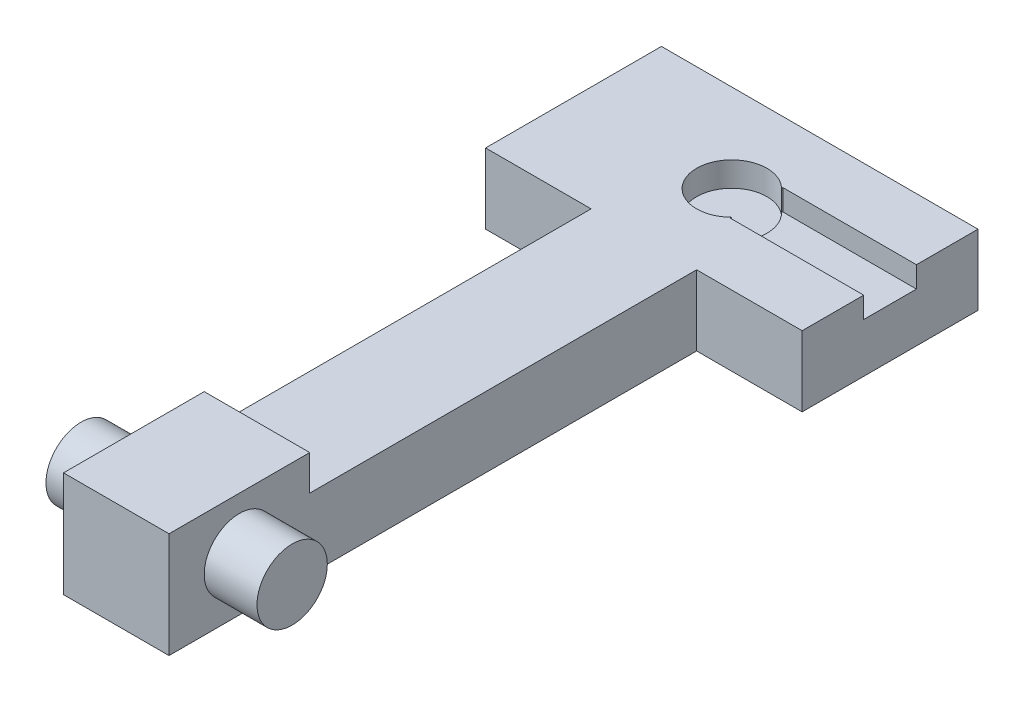
SolidWorks part; units mm, degrees
ref_plane "Front Plane" through (0, 0, 0) normal (0, 0, 1) x (1, 0, 0)
ref_plane "Top Plane" through (0, 0, 0) normal (0, 1, 0) x (1, 0, 0)
ref_plane "Right Plane" through (0, 0, 0) normal (1, 0, 0) x (0, 0, -1)
sketch "Sketch1" plane through (0, 0, 0) normal (0, 1, 0) x (1, 0, 0)
  line L0 (0, 0) -> (30, 0)
  line L1 (30, 0) -> (30, 150)
  line L2 (0, 0) -> (0, 150)
  line L4 (0, 150) -> (-30, 150)
  line L5 (-30, 150) -> (-30, 200)
  line L6 (-30, 200) -> (60, 200)
  line L7 (60, 200) -> (60, 150)
  line L8 (60, 150) -> (30, 150)
  dimension "D1" = 150
  dimension "D2" = 30
  dimension "D3" = 30
  dimension "D4" = 50
extrude "Boss-Extrude1" add sketch "Sketch1" along normal blind 20
sketch "Sketch2" plane through (0, 20, 0) normal (0, 1, 0) x (1, 0, 0)
  line L1 (0, 0) -> (30, 0) construction
  line L2 (15, 0) -> (15, 200) construction
  line L3 (60, 200) -> (-30, 200) construction
  line L4 (60, 175) -> (-30, 175) construction
  line L5 (60, 150) -> (60, 200) construction
  line L6 (-30, 200) -> (-30, 150) construction
  circle A0 centre (15, 175) radius 10
  point P14 (15, 111.206)
  dimension "D1" = 20
extrude "Cut-Extrude1" cut sketch "Sketch2" against normal blind 7
sketch "Sketch3" plane through (0, 20, 0) normal (0, 1, 0) x (1, 0, 0)
  line L0 (60, 150) -> (60, 200) construction
  line L1 (60, 182.5) -> (22, 182.5)
  line L2 (60, 182.5) -> (60, 167.5)
  line L3 (60, 167.5) -> (22, 167.5)
  line L4 (22, 182.5) -> (22, 167.5)
  line L5 (30, 150) -> (60, 150) construction
  dimension "D1" = 17.5
  dimension "D2" = 15
  dimension "D3" = 38
extrude "Cut-Extrude2" cut sketch "Sketch3" against normal blind 6
sketch "Sketch7" plane through (0, 20, 0) normal (0, 1, 0) x (1, 0, 0)
  line L0 (0, 150) -> (0, 0) construction
  line L1 (30, 0) -> (0, 0)
  line L2 (30, 0) -> (30, 40)
  line L3 (30, 40) -> (0, 40)
  line L4 (0, 0) -> (0, 40)
  dimension "D1" = 40
extrude "Boss-Extrude2" add sketch "Sketch7" along normal blind 10
sketch "Sketch8" plane through (30, 0, 0) normal (1, 0, 0) x (0, 0, -1)
  line L0 (20, 30) -> (20, 0) construction
  line L1 (0, 30) -> (40, 30) construction
  line L2 (0, 0) -> (150, 0) construction
  line L3 (0, 15) -> (38.6017, 15) construction
  line L4 (0, 30) -> (0, 0) construction
  circle A0 centre (20, 15) radius 10
  point P12 (0, 0)
  point P13 (0, 0)
  point P14 (20, 12.8134)
  dimension "D1" = 20
extrude "Boss-Extrude3" add sketch "Sketch8" along normal blind 15 and the other way blind 45
